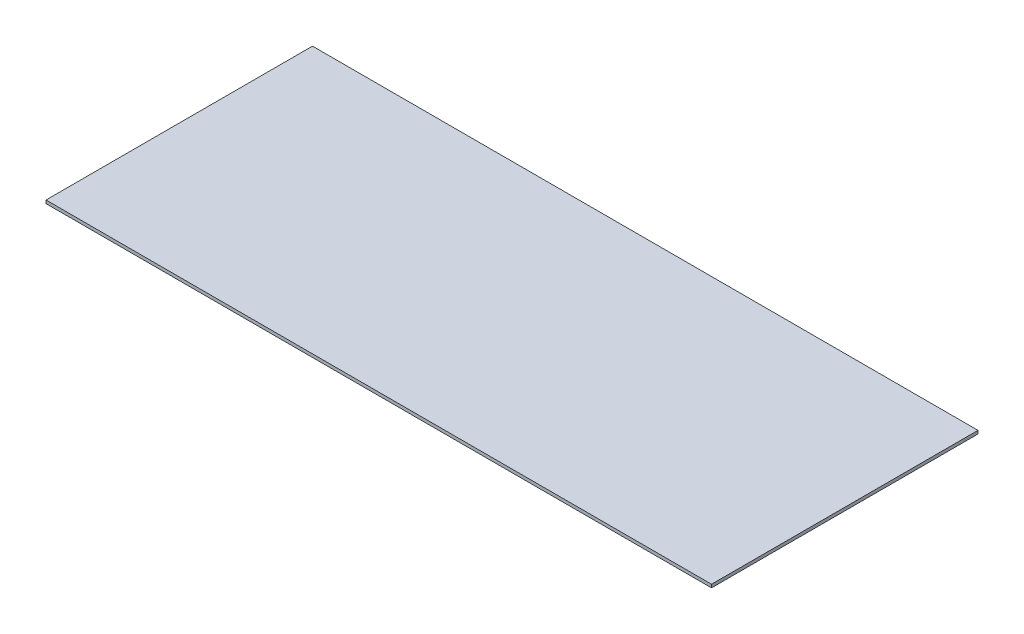
SolidWorks part; units mm, degrees
ref_plane "Front Plane" through (0, 0, 0) normal (0, 0, 1) x (1, 0, 0)
ref_plane "Top of Plywood" through (0, 0, 0) normal (0, 1, 0) x (1, 0, 0)
ref_plane "Right Plane" through (0, 0, 0) normal (1, 0, 0) x (0, 0, -1)
sketch "Interior Dim" plane through (0, 0, 0) normal (0, 1, 0) x (1, 0, 0)
  line L1 (0, 0) -> (5867.4, 0)
  line L2 (0, 0) -> (0, 2349.5)
  line L3 (0, 2349.5) -> (5867.4, 2349.5)
  line L4 (5867.4, 0) -> (5867.4, 2349.5)
  dimension "D1" = 5867.4
  dimension "D2" = 2349.5
sketch "Stud Centerlines" plane through (0, 0, 0) normal (0, 1, 0) x (1, 0, 0)
  line L0 (19.05, 19.05) -> (19.05, 2330.45) construction
  line L1 (19.05, 2330.45) -> (5867.4, 2330.45) construction
  line L2 (5867.4, 0) -> (5867.4, 2349.5) construction
  line L3 (5867.4, 19.05) -> (19.05, 19.05) construction
  line L4 (0, 0) -> (0, 2349.5) construction
  line L5 (0, 2349.5) -> (5867.4, 2349.5) construction
  line L6 (0, 0) -> (5867.4, 0) construction
  line L8 (3994.15, 2330.45) -> (3994.15, 19.05) construction
  line L9 (1797.05, 2330.45) -> (1797.05, 19.05) construction
  line L10 (19.05, 2051.05) -> (3994.15, 2051.05) construction
  dimension "D1" = 19.05
  dimension "D2" = 19.05
  dimension "D3" = 19.05
  dimension "D5" = 279.4
  dimension "D6" = 1778
  dimension "D7" = 2197.1
sketch "Gypsum Board" plane through (0, 0, 0) normal (0, 1, 0) x (1, 0, 0)
  line L0 (38.1, 38.1) -> (38.1, 2311.4)
  line L1 (38.1, 2311.4) -> (5867.4, 2311.4)
  line L2 (5867.4, 0) -> (5867.4, 2349.5) construction
  line L3 (50.8, 2298.7) -> (50.8, 50.8)
  line L4 (38.1, 38.1) -> (5867.4, 38.1)
  line L5 (50.8, 50.8) -> (5867.4, 50.8)
  line L6 (19.05, 19.05) -> (19.05, 2330.45) construction
  line L7 (19.05, 2330.45) -> (5867.4, 2330.45) construction
  line L8 (5867.4, 19.05) -> (19.05, 19.05) construction
  line L9 (4038.6, 50.8) -> (4038.6, 2095.5)
  line L10 (50.8, 2298.7) -> (5867.4, 2298.7)
  line L11 (4038.6, 2095.5) -> (4051.3, 2095.5)
  line L12 (4051.3, 2095.5) -> (4051.3, 50.8)
  line L13 (3994.15, 2330.45) -> (3994.15, 19.05) construction
  line L14 (19.05, 2051.05) -> (3994.15, 2051.05) construction
  dimension "D1" = 19.05
  dimension "D2" = 19.05
  dimension "D3" = 12.7
  dimension "D4" = 12.7
  dimension "D5" = 12.7
  dimension "D6" = 19.05
  dimension "D7" = 44.45
  dimension "D8" = 12.7
  dimension "D9" = 44.45
sketch "PVC" plane through (0, 0, 0) normal (0, 1, 0) x (1, 0, 0)
  line L0 (50.8, 50.8) -> (50.8, 2006.6)
  line L1 (3949.7, 50.8) -> (1841.5, 50.8)
  line L2 (50.8, 50.8) -> (1752.6, 50.8)
  line L3 (1752.6, 50.8) -> (1752.6, 2006.6)
  line L4 (1752.6, 2006.6) -> (50.8, 2006.6)
  line L5 (50.8, 2298.7) -> (50.8, 50.8) construction
  line L6 (19.05, 2051.05) -> (3994.15, 2051.05) construction
  line L7 (1797.05, 2330.45) -> (1797.05, 19.05) construction
  line L8 (50.8, 50.8) -> (5867.4, 50.8) construction
  line L9 (63.5, 1993.9) -> (1739.9, 1993.9)
  line L10 (1739.9, 1993.9) -> (1739.9, 63.5)
  line L11 (1739.9, 63.5) -> (63.5, 63.5)
  line L12 (63.5, 63.5) -> (63.5, 1993.9)
  line L13 (1841.5, 2006.6) -> (3949.7, 2006.6)
  line L14 (3949.7, 2006.6) -> (3949.7, 50.8)
  line L15 (1841.5, 50.8) -> (1841.5, 2006.6)
  line L16 (3994.15, 2330.45) -> (3994.15, 19.05) construction
  line L17 (1854.2, 1993.9) -> (1854.2, 63.5)
  line L18 (1854.2, 63.5) -> (3937, 63.5)
  line L19 (3937, 63.5) -> (3937, 1993.9)
  line L20 (3937, 1993.9) -> (1854.2, 1993.9)
  dimension "D1" = 0
  dimension "D2" = 44.45
  dimension "D3" = 44.45
  dimension "D4" = 0
  dimension "D5" = 12.7
  dimension "D6" = 12.7
  dimension "D7" = 12.7
  dimension "D8" = 12.7
  dimension "D9" = 44.45
  dimension "D10" = 44.45
  dimension "D11" = 12.7
  dimension "D12" = 12.7
  dimension "D13" = 12.7
  dimension "D14" = 12.7
sketch "Open Indoor Space" plane through (0, 0, 0) normal (0, 1, 0) x (1, 0, 0)
  line L0 (4051.3, 2095.5) -> (4038.6, 2095.5)
  line L1 (63.5, 63.5) -> (1739.9, 63.5)
  line L2 (63.5, 63.5) -> (63.5, 1993.9)
  line L3 (63.5, 1993.9) -> (1739.9, 1993.9)
  line L4 (1739.9, 63.5) -> (1739.9, 1993.9)
  line L5 (1854.2, 63.5) -> (3937, 63.5)
  line L6 (1854.2, 63.5) -> (1854.2, 1993.9)
  line L7 (1854.2, 1993.9) -> (3937, 1993.9)
  line L8 (3937, 63.5) -> (3937, 1993.9)
  line L9 (4038.6, 2095.5) -> (50.8, 2095.5)
  line L10 (50.8, 2298.7) -> (50.8, 50.8) construction
  line L11 (50.8, 2095.5) -> (50.8, 2298.7)
  line L12 (50.8, 2298.7) -> (5867.4, 2298.7)
  line L13 (5867.4, 2298.7) -> (5867.4, 50.8)
  line L14 (5867.4, 50.8) -> (4051.3, 50.8)
  line L15 (4051.3, 50.8) -> (4051.3, 2095.5)
ref_plane "Interior Roof" through (0, 2381.25, 0) normal (0, 1, 0) x (1, 0, 0)
sketch "Sketch4" plane through (0, 0, 0) normal (0, 1, 0) x (1, 0, 0)
  line L1 (0, 0) -> (5867.4, 0)
  line L2 (0, 0) -> (0, 2349.5)
  line L3 (0, 2349.5) -> (5867.4, 2349.5)
  line L4 (5867.4, 0) -> (5867.4, 2349.5)
extrude "Boss-Extrude2" add sketch "Sketch4" against normal blind 27.94
sketch "Sketch5" plane through (0, 0, 0) normal (0, 1, 0) x (1, 0, 0)
  line L0 (177.8, 63.5) -> (177.8, 0)
  line L1 (1739.9, 63.5) -> (63.5, 63.5) construction
  line L2 (0, 0) -> (5867.4, 0) construction
  line L3 (1168.4, 63.5) -> (1168.4, 0)
  line L4 (63.5, 63.5) -> (63.5, 1993.9) construction
  line L5 (546.1, 1993.9) -> (546.1, 1701.3979)
  line L6 (63.5, 1993.9) -> (1739.9, 1993.9) construction
  line L7 (1797.05, 520.7) -> (1739.9, 520.7)
  line L9 (1797.05, 2330.45) -> (1797.05, 19.05) construction
  line L10 (1739.9, 1993.9) -> (1739.9, 63.5) construction
  point P20 (1768.475, 520.7)
  dimension "D1" = 990.6
  dimension "D2" = 114.3
  dimension "D3" = 482.6
  dimension "D4" = 457.2
